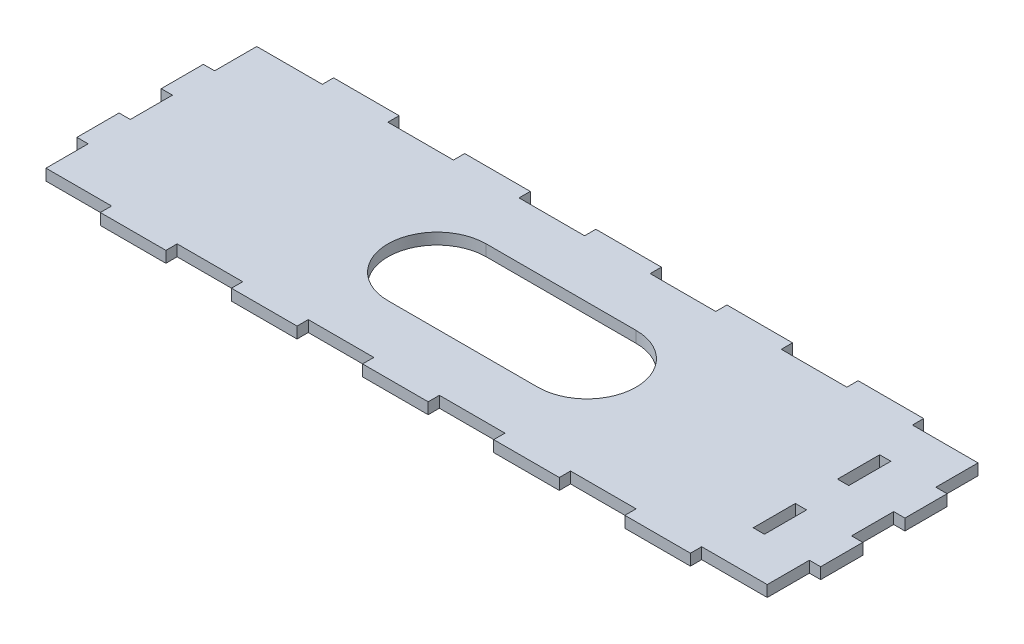
SolidWorks part; units mm, degrees
ref_plane "Front Plane" through (0, 0, 0) normal (0, 0, 1) x (1, 0, 0)
ref_plane "Top Plane" through (0, 0, 0) normal (0, 1, 0) x (1, 0, 0)
ref_plane "Right Plane" through (0, 0, 0) normal (1, 0, 0) x (0, 0, -1)
sketch "Sketch1" plane through (0, 0, 0) normal (0, 1, 0) x (1, 0, 0)
  line L1 (-192.5, -56.25) -> (192.5, -56.25)
  line L2 (-192.5, -56.25) -> (-192.5, 56.25)
  line L3 (-192.5, 56.25) -> (192.5, 56.25)
  line L4 (192.5, -56.25) -> (192.5, 56.25)
  line L5 (-192.5, -56.25) -> (192.5, 56.25) construction
  line L6 (-192.5, 56.25) -> (192.5, -56.25) construction
  point P0 (0, 0)
  dimension "D1" = 385
  dimension "D2" = 112.5
extrude "Boss-Extrude1" add sketch "Sketch1" along normal blind 6
sketch "Sketch2" plane through (-192.5, 0, 0) normal (-1, 0, 0) x (0, 0, 1)
  line L0 (-56.25, 6) -> (56.25, 6) construction
  line L1 (-56.25, 0) -> (-33.75, 0) construction
  line L2 (-56.25, 0) -> (-56.25, 6)
  line L3 (-56.25, 6) -> (-33.75, 6)
  line L4 (-33.75, 0) -> (-33.75, 6)
  line L5 (-56.25, 0) -> (56.25, 0) construction
  line L6 (-33.75, 6) -> (-11.25, 6)
  line L7 (-33.75, 6) -> (-33.75, 0)
  line L8 (-33.75, 0) -> (-11.25, 0)
  line L9 (-11.25, 6) -> (-11.25, 0)
  line L11 (-11.25, 0) -> (11.25, 0) construction
  line L12 (-11.25, 0) -> (-11.25, 6)
  line L13 (-11.25, 6) -> (11.25, 6)
  line L14 (11.25, 0) -> (11.25, 6)
  line L15 (11.25, 6) -> (33.75, 6)
  line L16 (11.25, 6) -> (11.25, 0)
  line L17 (11.25, 0) -> (33.75, 0)
  line L18 (33.75, 6) -> (33.75, 0)
  line L19 (33.75, 0) -> (56.25, 0) construction
  line L20 (33.75, 0) -> (33.75, 6)
  line L21 (33.75, 6) -> (56.25, 6)
  line L22 (56.25, 0) -> (56.25, 6)
  line M9 (-56.25, 0) -> (56.25, 0)
  line M11 (56.25, 6) -> (-56.25, 6)
extrude "Boss-Extrude2" add sketch "Sketch2" along normal blind 6 contours L9 L4 M11 M9 | L18 L14 M11 M9 region at (-192.5, 3, -22.5) region at (-192.5, 3, 22.5)
mirror "Mirror1" about plane through (0, 0, 0) normal (1, 0, 0) of "Boss-Extrude2"
sketch "Sketch3" plane through (0, 0, -56.25) normal (0, 0, -1) x (-1, 0, 0)
  line L0 (-192.5, 0) -> (192.5, 0) construction
  line L1 (192.5, 6) -> (157.5, 6)
  line L2 (192.5, 6) -> (192.5, 0)
  line L3 (192.5, 0) -> (157.5, 0)
  line L4 (157.5, 6) -> (157.5, 0)
  line L5 (-192.5, 6) -> (192.5, 6) construction
  line L6 (157.5, 0) -> (122.5, 0)
  line L7 (157.5, 0) -> (157.5, 6)
  line L8 (157.5, 6) -> (122.5, 6)
  line L9 (122.5, 0) -> (122.5, 6)
  line L11 (122.5, 6) -> (87.5, 6)
  line L12 (122.5, 6) -> (122.5, 0)
  line L13 (122.5, 0) -> (87.5, 0)
  line L14 (87.5, 6) -> (87.5, 0)
  line L15 (87.5, 0) -> (52.5, 0)
  line L16 (87.5, 0) -> (87.5, 6)
  line L17 (87.5, 6) -> (52.5, 6)
  line L18 (52.5, 0) -> (52.5, 6)
  line L19 (52.5, 6) -> (17.5, 6)
  line L20 (52.5, 6) -> (52.5, 0)
  line L21 (52.5, 0) -> (17.5, 0)
  line L22 (17.5, 6) -> (17.5, 0)
  line L23 (17.5, 0) -> (-17.5, 0)
  line L24 (17.5, 0) -> (17.5, 6)
  line L25 (17.5, 6) -> (-17.5, 6)
  line L26 (-17.5, 0) -> (-17.5, 6)
  line L27 (-17.5, 6) -> (-52.5, 6)
  line L28 (-17.5, 6) -> (-17.5, 0)
  line L29 (-17.5, 0) -> (-52.5, 0)
  line L30 (-52.5, 6) -> (-52.5, 0)
  line L31 (-52.5, 0) -> (-87.5, 0)
  line L32 (-52.5, 0) -> (-52.5, 6)
  line L33 (-52.5, 6) -> (-87.5, 6)
  line L34 (-87.5, 0) -> (-87.5, 6)
  line L35 (-87.5, 6) -> (-122.5, 6)
  line L36 (-87.5, 6) -> (-87.5, 0)
  line L37 (-87.5, 0) -> (-122.5, 0)
  line L38 (-122.5, 6) -> (-122.5, 0)
  line L39 (-122.5, 0) -> (-157.5, 0)
  line L40 (-122.5, 0) -> (-122.5, 6)
  line L41 (-122.5, 6) -> (-157.5, 6)
  line L42 (-157.5, 0) -> (-157.5, 6)
  line L43 (-157.5, 6) -> (-192.5, 6)
  line L44 (-157.5, 6) -> (-157.5, 0)
  line L45 (-157.5, 0) -> (-192.5, 0)
  line L46 (-192.5, 6) -> (-192.5, 0)
  point P29 (-138.6727, 0)
  point P31 (55.1684, 0)
  point P32 (-93.1142, 0)
  line M30 (-192.5, 0) -> (192.5, 0)
  line M32 (192.5, 6) -> (-192.5, 6)
extrude "Boss-Extrude3" add sketch "Sketch3" along normal blind 6 contours L9 L4 M30 M32 | L18 L14 M30 M32 | L26 L22 M30 M32 | L34 L30 M30 M32 | L42 L38 M30 M32 region at (-140, 3, -56.25) region at (-70, 3, -56.25) region at (0, 3, -56.25) region at (70, 3, -56.25) region at (140, 3, -56.25)
mirror "Mirror2" about plane through (0, 0, 0) normal (0, 0, 1) of "Boss-Extrude3"
sketch "Sketch4" plane through (0, 0, 0) normal (0, -1, 0) x (1, 0, 0)
  line L1 (162.5, 33.75) -> (168.5, 33.75)
  line L2 (162.5, 33.75) -> (162.5, 11.25)
  line L3 (162.5, 11.25) -> (168.5, 11.25)
  line L4 (168.5, 33.75) -> (168.5, 11.25)
  line L5 (168.5, -11.25) -> (162.5, -11.25)
  line L6 (168.5, -11.25) -> (168.5, -33.75)
  line L7 (168.5, -33.75) -> (162.5, -33.75)
  line L8 (162.5, -11.25) -> (162.5, -33.75)
extrude "Cut-Extrude1" cut sketch "Sketch4" against normal blind 6
sketch "Sketch5" plane through (0, 6, 0) normal (0, 1, 0) x (1, 0, 0)
  line L0 (40, 0) -> (-40, 0) construction
  line L1 (40, -26.25) -> (-40, -26.25)
  line L2 (40, 26.25) -> (-40, 26.25)
  line L3 (-120.1697, 56.25) -> (120.1697, 56.25) construction
  arc A0 (40, -26.25) -> (40, 26.25) centre (40, 0) ccw
  arc A1 (-40, 26.25) -> (-40, -26.25) centre (-40, 0) ccw
  point P2 (0, 0)
  dimension "D1" = 30
  dimension "D2" = 80
extrude "Cut-Extrude2" cut sketch "Sketch5" against normal through all
